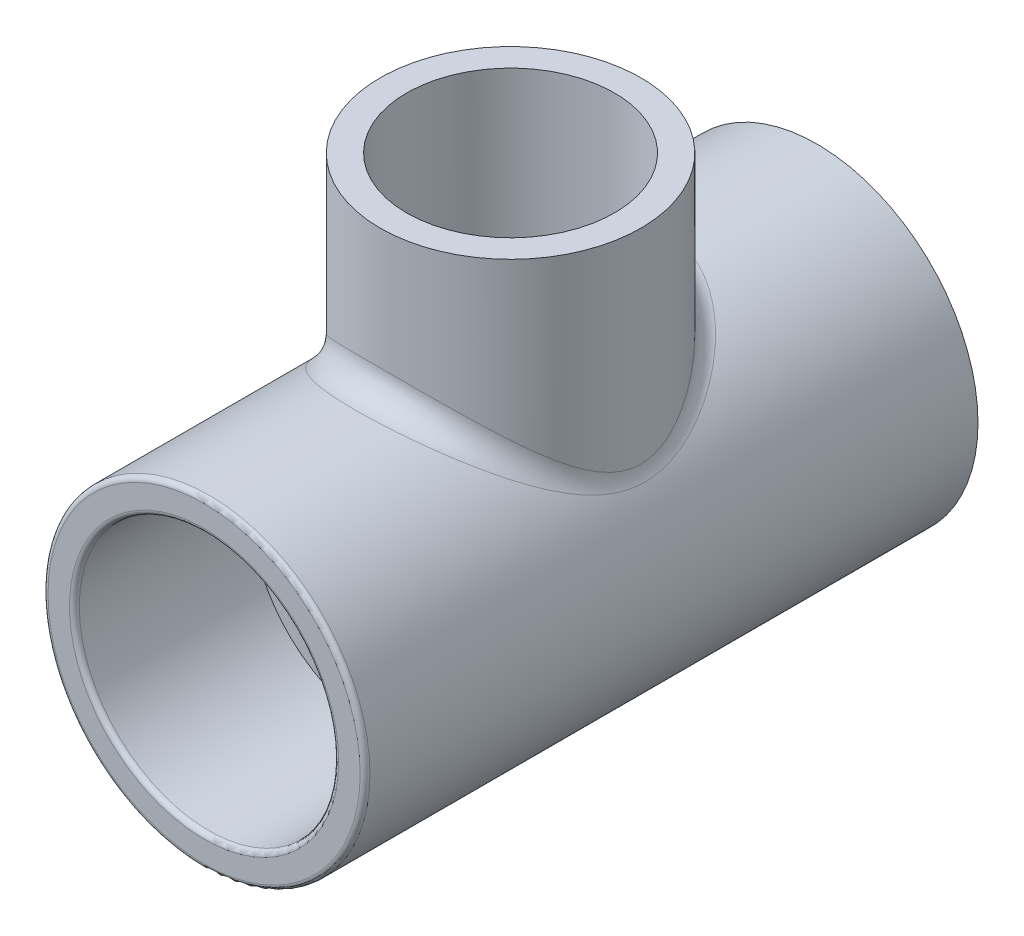
SolidWorks part; units mm, degrees
ref_plane "Front Plane" through (0, 0, 0) normal (0, 0, 1) x (1, 0, 0)
ref_plane "Top Plane" through (0, 0, 0) normal (0, 1, 0) x (1, 0, 0)
ref_plane "Right Plane" through (0, 0, 0) normal (1, 0, 0) x (0, 0, -1)
sketch "Sketch1" plane through (0, 0, 0) normal (0, 0, 1) x (1, 0, 0)
  circle A0 centre (0, 0) radius 656.5
  dimension "D1" = 1313
extrude "Boss-Extrude1" add sketch "Sketch1" along normal blind 1250 and the other way blind 1250
sketch "Sketch2" plane through (0, 0, 0) normal (0, 1, 0) x (1, 0, 0)
  circle A0 centre (0, 0) radius 531.5
  dimension "D1" = 1063
extrude "Boss-Extrude2" add sketch "Sketch2" along normal blind 1250
sketch "Sketch3" plane through (0, 1250, 0) normal (0, 1, 0) x (1, 0, 0)
  circle A0 centre (0, 0) radius 311
  dimension "D1" = 622
extrude "Cut-Extrude1" cut sketch "Sketch3" against normal through all
sketch "Sketch4" plane through (0, 1250, 0) normal (0, 1, 0) x (1, 0, 0)
  circle A0 centre (0, 0) radius 424
  dimension "D1" = 848
extrude "Cut-Extrude2" cut sketch "Sketch4" against normal through all
sketch "Sketch5" plane through (0, 0, -1250) normal (0, 0, -1) x (-1, 0, 0)
  circle A0 centre (0, 0) radius 412
  dimension "D1" = 824
extrude "Cut-Extrude3" cut sketch "Sketch5" against normal through all
sketch "Sketch6" plane through (0, 0, -1250) normal (0, 0, -1) x (-1, 0, 0)
  circle A0 centre (0, 0) radius 529
  dimension "D1" = 1058
extrude "Cut-Extrude4" cut sketch "Sketch6" against normal blind 720
fillet "Fillet1" radius 20 1 edges at (-529, 0, -1250)
sketch "Sketch7" plane through (0, 0, 1250) normal (0, 0, 1) x (1, 0, 0)
  circle A0 centre (0, 0) radius 529
  dimension "D1" = 1058
extrude "Cut-Extrude5" cut sketch "Sketch7" against normal blind 720
fillet "Fillet2" radius 20 2 edges at (656.5, 0, 1250) (529, 0, 1250)
fillet "Fillet3" radius 100 1 edges at (-51.7907, 654.454, 528.9707)
